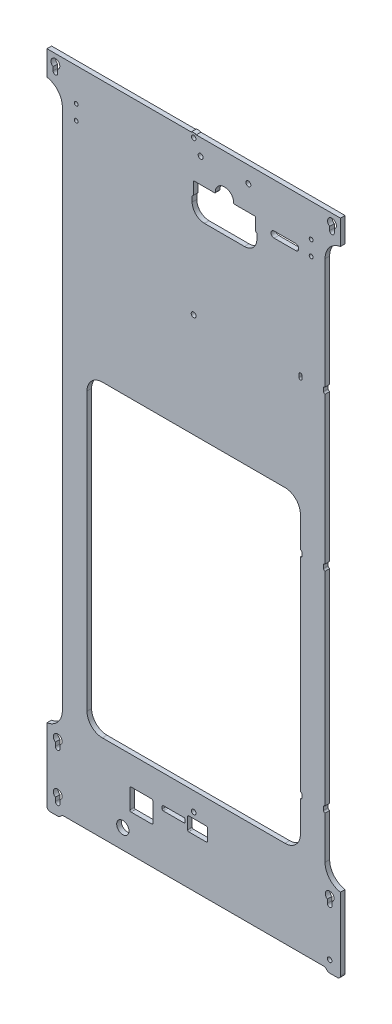
SolidWorks part; units mm, degrees
material "6061-T6 Black anodised"
ref_plane "Front Plane" through (0, 0, 0) normal (0, 0, 1) x (1, 0, 0)
ref_plane "Top Plane" through (0, 0, 0) normal (0, 1, 0) x (1, 0, 0)
ref_plane "Right Plane" through (0, 0, 0) normal (1, 0, 0) x (0, 0, -1)
sketch "Sketch1" plane through (0, 0, 0) normal (0, 0, 1) x (1, 0, 0)
  line L0 (88.27, 0) -> (-88.27, 0) construction
  line L1 (95.27, 389.5) -> (-95.27, 389.5)
  line L2 (95.27, 389.5) -> (95.27, -36.5)
  line L3 (85.27, -36.5) -> (-85.27, -36.5)
  line L4 (-95.27, 389.5) -> (-95.27, -36.5)
  line L5 (95.27, 389.5) -> (-95.27, -36.5) construction
  line L6 (95.27, -36.5) -> (-95.27, 389.5) construction
  line L7 (-89.77, -31) -> (-89.77, -28.5767)
  line L8 (-89.77, 379) -> (89.77, 379) construction
  line L9 (0, 379) -> (0, 0) construction
  line L10 (-86.77, -31) -> (-86.77, -28.5767)
  line L11 (-89.77, 0) -> (-89.77, 2.4233)
  line L12 (-86.77, 0) -> (-86.77, 2.4233)
  line L13 (86.77, -31) -> (86.77, -28.5767) construction
  line L14 (89.77, -31) -> (89.77, -28.5767) construction
  line L15 (86.77, 0) -> (86.77, 2.4233)
  line L16 (89.77, 0) -> (89.77, 2.4233)
  line L17 (88.27, 379) -> (88.27, 381.4233)
  line L18 (91.27, 379) -> (91.27, 381.4233)
  line L19 (-91.27, 379) -> (-91.27, 381.4233)
  line L20 (-88.27, 379) -> (-88.27, 381.4233)
  line L21 (95.27, -38.5) -> (87.27, -38.5)
  line L22 (87.27, -38.5) -> (85.27, -36.5)
  line L23 (-95.27, -38.5) -> (-87.27, -38.5)
  line L24 (-87.27, -38.5) -> (-85.27, -36.5)
  line L25 (-95.27, -36.5) -> (-95.27, -38.5)
  line L26 (95.27, -36.5) -> (95.27, -38.5)
  arc A0 (-89.77, 0) -> (-86.77, 0) centre (-88.27, 0) ccw
  arc A1 (86.77, 0) -> (89.77, 0) centre (88.27, 0) ccw
  arc A2 (-89.77, -31) -> (-86.77, -31) centre (-88.27, -31) ccw
  arc A3 (86.77, -31) -> (89.77, -31) centre (88.27, -31) ccw construction
  arc A4 (-91.27, 379) -> (-88.27, 379) centre (-89.77, 379) ccw
  arc A5 (88.27, 379) -> (91.27, 379) centre (89.77, 379) ccw
  arc A6 (-86.77, -28.5767) -> (-89.77, -28.5767) centre (-88.27, -26.1534) ccw
  circle A7 centre (-88.27, -31) radius 2.85 construction
  arc A8 (-86.77, 2.4233) -> (-89.77, 2.4233) centre (-88.27, 4.8466) ccw
  circle A9 centre (-88.27, 0) radius 2.85 construction
  arc A10 (89.77, -28.5767) -> (86.77, -28.5767) centre (88.27, -26.1534) ccw construction
  circle A11 centre (88.27, -31) radius 2.85 construction
  arc A12 (89.77, 2.4233) -> (86.77, 2.4233) centre (88.27, 4.8466) ccw
  circle A13 centre (88.27, 0) radius 2.85 construction
  arc A14 (91.27, 381.4233) -> (88.27, 381.4233) centre (89.77, 383.8466) ccw
  circle A15 centre (89.77, 379) radius 2.85 construction
  arc A16 (-88.27, 381.4233) -> (-91.27, 381.4233) centre (-89.77, 383.8466) ccw
  circle A17 centre (-89.77, 379) radius 2.85 construction
  circle A18 centre (88.27, -31) radius 1.5
  point P0 (0, 176.5)
  dimension "D4" = 3
  dimension "D9" = 5.7
  dimension "D7" = 5.5
  dimension "D1" = 190.54
  dimension "D2" = 426
  dimension "D3" = 7
  dimension "D5" = 31
  dimension "D6" = 5.5
  dimension "D8" = 10.5
  dimension "D10" = 2
  dimension "D11" = 8
  dimension "D12" = 45
extrude "Boss-Extrude1" add sketch "Sketch1" along normal blind 3
sketch "Sketch2" plane through (0, 0, 3) normal (0, 0, 1) x (1, 0, 0)
  line L0 (-95.27, 389.5) -> (-95.27, -38.5) construction
  line L1 (-95.27, 10.5) -> (-85.27, 10.5)
  line L2 (-95.27, 10.5) -> (-95.27, 373.5)
  line L3 (-95.27, 373.5) -> (-85.27, 373.5)
  line L4 (-85.27, 10.5) -> (-85.27, 373.5)
  line L5 (95.27, -38.5) -> (95.27, 389.5) construction
  line L6 (95.27, 10.5) -> (85.27, 10.5)
  line L7 (95.27, 10.5) -> (95.27, 373.5)
  line L8 (95.27, 373.5) -> (85.27, 373.5)
  line L9 (85.27, 10.5) -> (85.27, 373.5)
  line L10 (95.27, 389.5) -> (-95.27, 389.5) construction
  line L11 (-85.27, -36.5) -> (85.27, -36.5) construction
  dimension "D1" = 16
  dimension "D2" = 47
  dimension "D3" = 10
extrude "Cut-Extrude1" cut sketch "Sketch2" against normal through all
fillet "Fillet1" radius 12 4 edges at (85.27, 10.5, 1.5) (-85.27, 10.5, 1.5) (85.27, 373.5, 1.5) (-85.27, 373.5, 1.5)
sketch "Sketch3" plane through (0, 0, 3) normal (0, 0, 1) x (1, 0, 0)
  line L0 (-85.27, -36.5) -> (85.27, -36.5) construction
  line L1 (95.27, 389.5) -> (-95.27, 389.5) construction
  circle A0 centre (0, 8) radius 1.5
  circle A1 centre (-88.27, 0) radius 1.5 construction
  circle A2 centre (0, 387) radius 1.5
  dimension "D2" = 2.5
  dimension "D1" = 44.5
extrude "Cut-Extrude2" cut sketch "Sketch3" against normal through all
sketch "Sketch4" plane through (0, 0, 3) normal (0, 0, 1) x (1, 0, 0)
  line L0 (-85.27, 22.3322) -> (-85.27, 361.6678) construction
  line L1 (-69.27, 220) -> (69.27, 220)
  line L2 (-69.27, 220) -> (-69.27, 20)
  line L3 (-69.27, 20) -> (69.27, 20)
  line L4 (69.27, 220) -> (69.27, 20)
  line L5 (-69.27, 220) -> (69.27, 20) construction
  line L6 (-69.27, 20) -> (69.27, 220) construction
  circle A0 centre (0, 8) radius 1.5 construction
  point P0 (0, 120)
  dimension "D1" = 16
  dimension "D2" = 12
  dimension "D3" = 200
extrude "Cut-Extrude3" cut sketch "Sketch4" against normal through all
fillet "Fillet2" radius 10 4 edges at (69.27, 220, 1.5) (-69.27, 220, 1.5) (69.27, 20, 1.5) (-69.27, 20, 1.5)
sketch "Sketch5" plane through (0, 0, 3) normal (0, 0, 1) x (1, 0, 0)
  line L0 (-46, 8.2274) -> (-46, -20.9664) construction
  line L6 (-41.5, 1.7) -> (-26.5, 1.7)
  line L7 (-41.5, 1.7) -> (-41.5, -12.4)
  line L8 (-41.5, -12.4) -> (-26.5, -12.4)
  line L9 (-26.5, 1.7) -> (-26.5, -12.4)
  line L10 (-20.5, 1.7) -> (-5.5, 1.7)
  line L11 (-20.5, 1.7) -> (-20.5, -1.3)
  line L12 (-20.5, -1.3) -> (-5.5, -1.3)
  line L13 (-5.5, 1.7) -> (-5.5, -1.3)
  line L14 (-4, 4.2) -> (9, 4.2)
  line L15 (-4, 4.2) -> (-4, -4.8)
  line L16 (-4, -4.8) -> (9, -4.8)
  line L17 (9, 4.2) -> (9, -4.8)
  circle A1 centre (0, 8) radius 1.5 construction
  dimension "D3" = 2.5
  dimension "D2" = 6.3
  dimension "D5" = 46
  dimension "D6" = 4.5
  dimension "D7" = 15
  dimension "D8" = 25.5
  dimension "D9" = 15
  dimension "D10" = 42
  dimension "D11" = 13
  dimension "D12" = 14.1
  dimension "D13" = 3
  dimension "D14" = 9
extrude "Cut-Extrude4" cut sketch "Sketch5" against normal through all
fillet "Fillet3" radius 0.8 12 edges at (9, -4.8, 1.5) (9, 4.2, 1.5) (-4, 4.2, 1.5) (-4, -4.8, 1.5) (-5.5, -1.3, 1.5) (-5.5, 1.7, 1.5) (-20.5, 1.7, 1.5) (-20.5, -1.3, 1.5) (-26.5, -12.4, 1.5) (-26.5, 1.7, 1.5) (-41.5, 1.7, 1.5) (-41.5, -12.4, 1.5)
sketch "Sketch6" plane through (0, 0, 3) normal (0, 0, 1) x (1, 0, 0)
  circle A0 centre (-46, -23.8) radius 4
  circle A1 centre (0, 8) radius 1.5 construction
  dimension "D2" = 8
  dimension "D3" = 31.8
  dimension "D1" = 46
extrude "Cut-Extrude5" cut sketch "Sketch6" against normal through all
sketch "Sketch7" plane through (0, 0, 3) normal (0, 0, 1) x (1, 0, 0)
  line L0 (0, -35.055) -> (-4.8534, -39.9081)
  line L1 (6.0015, -39.9081) -> (0.8516, -35.055)
  line L2 (-7.2622, -33.0882) -> (7.8165, -33.0882)
  line L3 (8.077, -32.9782) -> (11.0039, -30.0512)
  line L4 (10.2253, -29.347) -> (-7.2622, -29.347)
  line L5 (-14.4113, -36.4965) -> (-14.4098, -53.9837)
  line L6 (-13.7057, -54.7607) -> (-10.7801, -51.8338)
  line L7 (-10.6686, -51.5749) -> (-10.67, -36.4965)
  line L8 (8.1139, -55.2833) -> (-6.9645, -55.2833)
  line L9 (-7.2249, -55.3948) -> (-10.1519, -58.3217)
  line L10 (-9.3733, -59.0259) -> (8.1139, -59.0259)
  line L11 (15.2633, -51.8752) -> (15.2619, -34.3893)
  line L12 (14.5577, -33.6121) -> (11.6308, -36.5391)
  line L13 (11.5207, -36.798) -> (11.5218, -51.8752)
  spline S0 degree 3 poles (0.4439, -34.8701) (0.3912, -34.8752) (0.2828, -34.8857) (0.1286, -34.9495) (0.0426, -35.02) (0, -35.055) knots 0 0 0 0 0.322338 0.663828 1 1 1 1
  spline S1 degree 3 poles (-4.8534, -39.9081) (-4.8579, -39.9123) (-4.8667, -39.9205) (-4.8791, -39.9329) (-5.3375, -40.4392) (-6.231, -41.4846) (-7.3312, -43.289) (-7.8887, -46.1117) (-6.8483, -49.6491) (-3.8783, -52.5981) (0.2577, -53.8719) (4.5569, -52.8137) (7.7118, -49.6441) (8.7217, -46.1226) (8.2109, -43.3277) (7.2971, -41.454) (6.4234, -40.4116) (6.0015, -39.9081) knots 0 0 0 0 0.000489 0.000958 0.001407 0.055151 0.111018 0.168413 0.280621 0.389777 0.490762 0.614387 0.723194 0.83533 0.891393 0.947551 1 1 1 1
  spline S2 degree 3 poles (0.8516, -35.055) (0.8125, -35.0211) (0.7352, -34.9541) (0.5954, -34.8849) (0.4944, -34.875) (0.4439, -34.8701) knots 0 0 0 0 0.338885 0.669777 1 1 1 1
  spline S3 degree 3 poles (7.8165, -33.0882) (7.8386, -33.0865) (7.882, -33.0833) (7.9472, -33.0756) (7.9964, -33.0496) (8.0324, -33.0241) (8.0557, -33.0007) (8.07, -32.9856) (8.077, -32.9782) knots 0 0 0 0 0.227493 0.445972 0.663373 0.787115 0.896006 1 1 1 1
  spline S4 degree 3 poles (11.0039, -30.0512) (11.0329, -30.0119) (11.0909, -29.9332) (11.1149, -29.785) (11.0877, -29.6491) (11.0204, -29.5396) (10.9299, -29.4607) (10.7969, -29.4113) (10.6368, -29.379) (10.4517, -29.3457) (10.3213, -29.3482) (10.25, -29.3467) (10.2377, -29.3461) (10.2294, -29.3467) (10.2253, -29.347) knots 0 0 0 0 0.104345 0.208931 0.313565 0.397995 0.482811 0.567894 0.701187 0.836715 0.973247 0.982163 0.991064 1 1 1 1
  spline S5 degree 3 poles (-7.2622, -29.347) (-8.5111, -29.5465) (-10.9772, -29.9405) (-13.8177, -32.781) (-14.2117, -35.2473) (-14.4113, -36.4965) knots 0 0 0 0 0.336154 0.663772 1 1 1 1
  spline S6 degree 3 poles (-14.4098, -53.9837) (-14.4101, -53.9877) (-14.4107, -53.9955) (-14.4101, -54.0074) (-14.4085, -54.0786) (-14.4116, -54.2092) (-14.3778, -54.3947) (-14.348, -54.5555) (-14.2965, -54.6876) (-14.2178, -54.7779) (-14.1086, -54.8459) (-13.9724, -54.8732) (-13.8239, -54.8488) (-13.7451, -54.7901) (-13.7057, -54.7607) knots 0 0 0 0 0.008622 0.017031 0.025643 0.162638 0.298245 0.431901 0.516392 0.601007 0.685957 0.790142 0.895037 1 1 1 1
  spline S7 degree 3 poles (-10.7801, -51.8338) (-10.7711, -51.8245) (-10.7536, -51.8064) (-10.7264, -51.7794) (-10.6977, -51.7438) (-10.6778, -51.6947) (-10.6682, -51.6355) (-10.6685, -51.5956) (-10.6686, -51.5749) knots 0 0 0 0 0.131285 0.25763 0.390972 0.594165 0.788898 1 1 1 1
  spline S8 degree 3 poles (-10.67, -36.4965) (-10.5818, -35.8926) (-10.4093, -34.7122) (-9.0474, -33.3492) (-7.8666, -33.1766) (-7.2622, -33.0882) knots 0 0 0 0 0.33841 0.661392 1 1 1 1
  spline S9 degree 3 poles (-6.9645, -55.2833) (-6.9836, -55.284) (-7.0187, -55.2854) (-7.0727, -55.2938) (-7.117, -55.3142) (-7.157, -55.3379) (-7.1915, -55.3639) (-7.2134, -55.3842) (-7.2249, -55.3948) knots 0 0 0 0 0.196746 0.361608 0.557262 0.692766 0.839563 1 1 1 1
  spline S10 degree 3 poles (-10.1519, -58.3217) (-10.1809, -58.361) (-10.2389, -58.4397) (-10.2629, -58.5879) (-10.2357, -58.7239) (-10.1681, -58.8333) (-10.0777, -58.912) (-9.9452, -58.9619) (-9.7851, -58.9945) (-9.6, -59.0248) (-9.4695, -59.0303) (-9.3981, -59.025) (-9.3857, -59.0257) (-9.3774, -59.0258) (-9.3733, -59.0259) knots 0 0 0 0 0.104385 0.20895 0.313569 0.398093 0.483012 0.567612 0.700915 0.836485 0.973043 0.982112 0.991066 1 1 1 1
  spline S11 degree 3 poles (8.1139, -59.0259) (9.3629, -58.8263) (11.8293, -58.432) (14.6704, -55.5912) (15.064, -53.1244) (15.2633, -51.8752) knots 0 0 0 0 0.336157 0.663806 1 1 1 1
  spline S12 degree 3 poles (15.2619, -34.3893) (15.2622, -34.3852) (15.2628, -34.3769) (15.2621, -34.3644) (15.2606, -34.293) (15.2632, -34.1626) (15.2298, -33.9775) (15.198, -33.8174) (15.148, -33.6849) (15.0694, -33.5945) (14.9599, -33.5269) (14.8239, -33.4997) (14.6754, -33.5241) (14.597, -33.5828) (14.5577, -33.6121) knots 0 0 0 0 0.008953 0.017947 0.027021 0.163491 0.298949 0.432165 0.516776 0.601601 0.686035 0.790672 0.895263 1 1 1 1
  spline S13 degree 3 poles (11.6308, -36.5391) (11.6212, -36.5483) (11.6023, -36.5664) (11.5737, -36.5942) (11.5433, -36.6274) (11.5265, -36.6769) (11.5219, -36.7355) (11.5211, -36.7763) (11.5207, -36.798) knots 0 0 0 0 0.134582 0.264928 0.404991 0.586048 0.77989 1 1 1 1
  spline S14 degree 3 poles (11.5218, -51.8752) (11.4339, -52.4792) (11.262, -53.6599) (9.8992, -55.0226) (8.7183, -55.195) (8.1139, -55.2833) knots 0 0 0 0 0.338406 0.661372 1 1 1 1
extrude "Cut-Extrude6" [suppressed] cut sketch "Sketch7" against normal through all
sketch "Sketch8" plane through (0, 0, 3) normal (0, 0, 1) x (1, 0, 0)
  line L0 (-0.2, 358.725) -> (40.2, 358.725) construction
  line L1 (4.5, 378.9) -> (35.5, 378.9) construction
  line L2 (4.5, 378.9) -> (4.5, 347.9) construction
  line L3 (4.5, 347.9) -> (35.5, 347.9) construction
  line L4 (35.5, 378.9) -> (35.5, 347.9) construction
  line L5 (4.5, 378.9) -> (35.5, 347.9) construction
  line L6 (4.5, 347.9) -> (35.5, 378.9) construction
  line L7 (7, 342.4) -> (33, 342.4)
  line L8 (-1, 342.4) -> (-1, 384.4) construction
  line L9 (-1, 384.4) -> (41, 384.4) construction
  line L10 (41, 342.4) -> (41, 384.4) construction
  line L11 (-1, 342.4) -> (41, 384.4) construction
  line L12 (-1, 384.4) -> (41, 342.4) construction
  line L13 (14, 362.875) -> (-0.2, 362.875)
  line L14 (3, 362.875) -> (3, 354.575) construction
  line L15 (3, 354.575) -> (-0.2, 354.575) construction
  line L16 (-0.2, 362.875) -> (-0.2, 354.575)
  line L17 (20, 363.4) -> (20, 358.725) construction
  line L18 (14, 363.4) -> (14, 362.875)
  line L19 (40.2, 362.875) -> (26, 362.875)
  line L20 (40.2, 362.875) -> (40.2, 354.575)
  line L21 (40.2, 354.575) -> (37, 354.575) construction
  line L22 (37, 332.936) -> (37, 354.575) construction
  line L23 (59.27, 220) -> (-59.27, 220) construction
  line L24 (-0.2, 354.575) -> (-1, 353.775)
  line L25 (-1, 353.775) -> (-1, 350.4)
  line L26 (40.2, 354.575) -> (41, 353.775)
  line L27 (41, 353.775) -> (41, 350.4)
  line L28 (52.2, 358.725) -> (66.2, 358.725) construction
  line L29 (26, 362.875) -> (26, 363.4)
  line L30 (52.2, 360.725) -> (66.2, 360.725)
  line L31 (52.2, 356.725) -> (66.2, 356.725)
  circle A0 centre (4.5, 378.9) radius 1.6
  circle A1 centre (35.5, 378.9) radius 1.6
  circle A2 centre (35.5, 347.9) radius 1.6 construction
  circle A3 centre (4.5, 347.9) radius 1.6 construction
  circle A4 centre (0, 387) radius 1.5 construction
  arc A5 (41, 350.4) -> (33, 342.4) centre (33, 350.4) cw
  arc A6 (26, 363.4) -> (14, 363.4) centre (20, 363.4) ccw
  arc A7 (7, 342.4) -> (-1, 350.4) centre (7, 350.4) cw
  circle A8 centre (0, 287.5) radius 67.5 construction
  circle A9 centre (0, 287.5) radius 1.6
  arc A10 (52.2, 360.725) -> (52.2, 356.725) centre (52.2, 358.725) ccw
  arc A11 (66.2, 356.725) -> (66.2, 360.725) centre (66.2, 358.725) ccw
  point P0 (20, 363.4)
  point P9 (20, 363.4)
  point P48 (59.2, 358.725)
  dimension "D2" = 3.2
  dimension "D11" = 6
  dimension "D3" = 8
  dimension "D14" = 3.2
  dimension "D15" = 135
  dimension "D17" = 2
  dimension "D1" = 31
  dimension "D4" = 2.6
  dimension "D5" = 20
  dimension "D6" = 4.675
  dimension "D7" = 8.3
  dimension "D8" = 17
  dimension "D9" = 3.2
  dimension "D10" = 45
  dimension "D12" = 42
  dimension "D13" = 20.2
  dimension "D16" = 14
  dimension "D18" = 12
extrude "Cut-Extrude7" cut sketch "Sketch8" against normal through all
fillet "Fillet4" radius 0.4 4 edges at (40.2, 362.875, 1.5) (26, 362.875, 1.5) (-0.2, 362.875, 1.5) (14, 362.875, 1.5)
sketch "Sketch9" plane through (0, 0, 3) normal (0, 0, 1) x (1, 0, 0)
  line L0 (95.27, 389.5) -> (-95.27, 389.5) construction
  line L1 (-1.6583, 389.5) -> (1.6583, 389.5)
  arc A0 (1.6583, 389.5) -> (-1.6583, 389.5) centre (0, 387) ccw
  dimension "D1" = 3
extrude "Boss-Extrude2" add sketch "Sketch9" against normal up to surface (3 mm away) up to face at (59.2, 358.725, 0)
sketch "Sketch10" plane through (0, 0, 3) normal (0, 0, 1) x (1, 0, 0)
  line L0 (0, 387) -> (0, 368) construction
  line L1 (-76.27, 368) -> (76.27, 368) construction
  line L2 (-85.27, 22.3322) -> (-85.27, 361.6678) construction
  line L3 (-1.6583, 389.5) -> (-95.27, 389.5) construction
  circle A0 centre (-76.27, 368) radius 1.25
  circle A1 centre (-76.27, 358.5) radius 1.25
  circle A2 centre (76.27, 368) radius 1.25
  circle A3 centre (76.27, 358.5) radius 1.25
  dimension "D2" = 2.5
  dimension "D1" = 9.5
  dimension "D3" = 9
  dimension "D4" = 21.5
extrude "Cut-Extrude8" cut sketch "Sketch10" against normal through all
sketch "Sketch11" plane through (0, 0, 3) normal (0, 0, 1) x (1, 0, 0)
  line L0 (85.27, 189) -> (85.27, 187) construction
  line L1 (86.27, 189) -> (86.27, 187)
  line L2 (84.27, 189) -> (84.27, 187)
  line L4 (69.27, 189) -> (69.27, 187) construction
  line L5 (70.27, 189) -> (70.27, 187)
  line L7 (68.27, 189) -> (68.27, 187)
  line L8 (85.27, 288.5) -> (85.27, 286.5) construction
  line L9 (86.27, 288.5) -> (86.27, 286.5)
  line L10 (84.27, 288.5) -> (84.27, 286.5)
  line L11 (69.27, 288.5) -> (69.27, 286.5) construction
  line L12 (70.27, 288.5) -> (70.27, 286.5)
  line L13 (68.27, 288.5) -> (68.27, 286.5)
  line L14 (59.27, 220) -> (-59.27, 220) construction
  line L15 (85.27, 53) -> (85.27, 51) construction
  line L16 (86.27, 53) -> (86.27, 51)
  line L17 (84.27, 53) -> (84.27, 51)
  line L18 (69.27, 53) -> (69.27, 51) construction
  line L19 (70.27, 53) -> (70.27, 51)
  line L20 (68.27, 53) -> (68.27, 51)
  line L22 (85.27, 189) -> (69.27, 189) construction
  line L23 (85.27, 361.6678) -> (85.27, 22.3322) construction
  line L27 (-59.27, 20) -> (59.27, 20) construction
  arc A0 (86.27, 189) -> (84.27, 189) centre (85.27, 189) ccw
  arc A1 (84.27, 187) -> (86.27, 187) centre (85.27, 187) ccw
  arc A2 (70.27, 189) -> (68.27, 189) centre (69.27, 189) ccw
  arc A3 (68.27, 187) -> (70.27, 187) centre (69.27, 187) ccw
  arc A4 (86.27, 288.5) -> (84.27, 288.5) centre (85.27, 288.5) ccw
  arc A5 (84.27, 286.5) -> (86.27, 286.5) centre (85.27, 286.5) ccw
  arc A6 (70.27, 288.5) -> (68.27, 288.5) centre (69.27, 288.5) ccw
  arc A7 (68.27, 286.5) -> (70.27, 286.5) centre (69.27, 286.5) ccw
  arc A8 (86.27, 53) -> (84.27, 53) centre (85.27, 53) ccw
  arc A9 (84.27, 51) -> (86.27, 51) centre (85.27, 51) ccw
  arc A10 (70.27, 53) -> (68.27, 53) centre (69.27, 53) ccw
  arc A11 (68.27, 51) -> (70.27, 51) centre (69.27, 51) ccw
  point P2 (85.27, 188)
  point P12 (69.27, 188)
  point P19 (85.27, 287.5)
  point P26 (69.27, 287.5)
  point P35 (85.27, 52)
  point P42 (69.27, 52)
  point P49 (0, 287.5)
  dimension "D6" = 32
  dimension "D1" = 2
  dimension "D2" = 2
  dimension "D3" = 32
  dimension "D5" = 2
  dimension "D8" = 16
extrude "Cut-Extrude9" cut sketch "Sketch11" against normal through all
fillet "Fillet5" radius 2 6 edges at (85.27, -36.5, 1.5) (87.27, -38.5, 1.5) (95.27, -38.5, 1.5) (-85.27, -36.5, 1.5) (-87.27, -38.5, 1.5) (-95.27, -38.5, 1.5)
